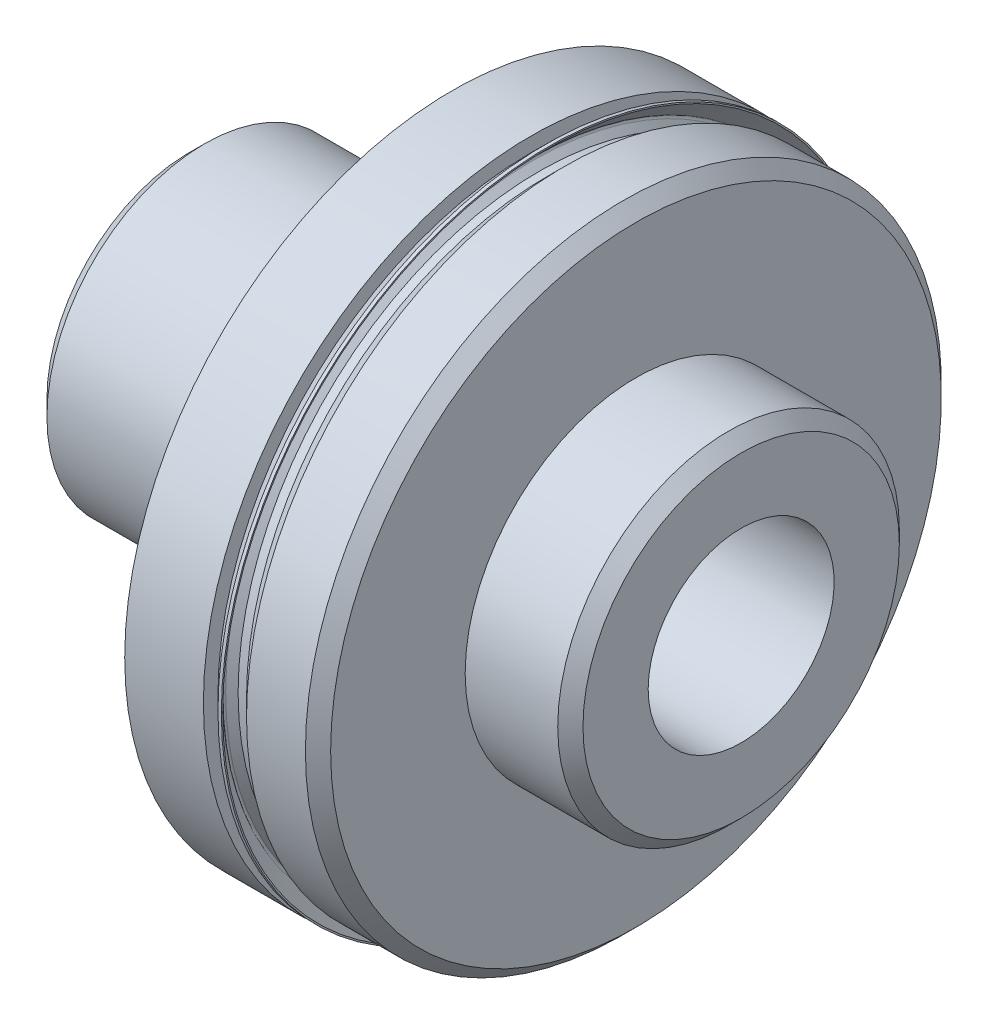
SolidWorks part; units mm, degrees
material "Cast Alloy Steel"
ref_plane "Front Plane" through (0, 0, 0) normal (0, 0, 1) x (1, 0, 0)
ref_plane "Top Plane" through (0, 0, 0) normal (0, 1, 0) x (1, 0, 0)
ref_plane "Right Plane" through (0, 0, 0) normal (1, 0, 0) x (0, 0, -1)
sketch "Sketch1" plane through (0, 0, 0) normal (0, 0, 1) x (1, 0, 0)
  line L0 (0, 0) -> (0, 8.589)
  line L1 (0, 8.589) -> (0.936, 9.525)
  line L2 (0.936, 9.525) -> (9.31, 9.525)
  line L3 (9.31, 9.525) -> (10.2623, 8.6108)
  line L4 (11.0363, 8.2995) -> (12.3698, 8.2995)
  line L5 (13.4874, 9.417) -> (13.4874, 9.4932)
  line L6 (13.4874, 9.4932) -> (15.875, 9.4932)
  line L7 (15.875, 9.4932) -> (15.875, 0)
  line L8 (15.875, 0) -> (0, 0)
  line L9 (15.875, 0) -> (0, 0) construction
  arc A0 (10.2623, 8.6108) -> (11.0363, 8.2995) centre (11.0363, 9.417) ccw
  arc A1 (12.3698, 8.2995) -> (13.4874, 9.417) centre (12.3698, 9.4171) ccw
revolve "Revolve1" add sketch "Sketch1" angle 360 about L9 reverse direction yes
cosmetic thread "Cosmetic Thread1" parameters "D1"=10.246, "D2"=17.178
sketch "Sketch2" plane through (0, 0, 0) normal (0, 0, 1) x (1, 0, 0)
  line L0 (15.875, 0) -> (15.875, 19.7676)
  line L1 (15.875, 19.7676) -> (20.6248, 19.7676)
  line L2 (20.6248, 19.7676) -> (20.6248, 18.1801)
  line L3 (20.6248, 18.1801) -> (21.6408, 18.1801)
  line L4 (21.6408, 18.1801) -> (22.6568, 19.196)
  line L5 (22.6568, 19.196) -> (26.2128, 19.196)
  line L6 (26.2128, 19.196) -> (26.9748, 18.434)
  line L7 (26.9748, 18.434) -> (26.9748, 0)
  line L8 (26.9748, 0) -> (15.875, 0)
  line L9 (26.9748, 0) -> (15.875, 0) construction
revolve "Revolve2" add sketch "Sketch2" angle 360 about L9 reverse direction yes
sketch "Sketch3" plane through (0, 0, 0) normal (0, 0, 1) x (1, 0, 0)
  line L0 (26.9748, 0) -> (26.9748, 10.3124)
  line L1 (26.9748, 10.3124) -> (32.5628, 10.3124)
  line L2 (32.5628, 10.3124) -> (33.3248, 9.5504)
  line L3 (33.3248, 9.5504) -> (33.3248, 0)
  line L4 (33.3248, 0) -> (26.9748, 0)
  line L5 (33.3248, 0) -> (26.9748, 0) construction
revolve "Revolve3" add sketch "Sketch3" angle 360 about L5 reverse direction yes
hole_wizard "Hole1" positions "Sketch5" profile "Sketch4" legacy
sketch "Sketch5" plane through (0, 0, 0) normal (-1, 0, 0) x (0, 0, 1)
  point P0 (0, 0)
sketch "Sketch4" plane through (0, 0, 0) normal (0, 1, 0) x (0, 0, 1)
  line L0 (0, 0) -> (0, 33.3248)
  line L1 (0, 33.3248) -> (5.6134, 33.3248)
  line L2 (5.6134, 33.3248) -> (5.6134, 0.762)
  line L3 (5.6134, 0.762) -> (6.3754, 0)
  line L4 (6.3754, 0) -> (0, 0)
  line L5 (0, -6.4453) -> (0, 115.525) construction
  line L6 (-5.6134, 0.762) -> (-6.3754, 0) construction
  dimension "Diameter" = 11.2268
  dimension "Depth" = 33.3248
  dimension "C-Sink Angle" = 90
  dimension "C-Sink Diameter" = 12.7508
ref_plane "Plane1" through (25.527, 0, 0) normal (1, 0, 0) x (0, 0, -1)
ref_plane "Plane2" through (25.527, 0, 0) normal (1, 0, 0) x (0, 0, -1)
ref_plane "Plane3" through (0, 0, 0) normal (0, -0.7071, 0.7071) x (1, 0, 0)
ref_plane "Plane4" through (3.1242, 0, 0) normal (1, 0, 0) x (0, 0, -1)
ref_plane "Plane5" through (20.6502, 0, 0) normal (1, 0, 0) x (0, 0, -1)
ref_plane "Plane6" through (15.875, 0, 0) normal (1, 0, 0) x (0, 0, -1)
ref_plane "Plane7" through (20.6502, 0, 0) normal (1, 0, 0) x (0, 0, -1)
sketch "Sketch6" plane through (0, 0, 0) normal (0, 0, 1) x (1, 0, 0)
  line L0 (20.6248, 17.9261) -> (21.6408, 17.9261)
  line L1 (21.6408, 17.9261) -> (21.6408, 18.1801)
  line L2 (21.6408, 18.1801) -> (21.1328, 18.1801)
  line L3 (21.1328, 18.1801) -> (20.7582, 18.5547)
  line L4 (20.7582, 18.7343) -> (21.7073, 19.6834)
  line L5 (21.7073, 19.6834) -> (21.7073, 19.7676)
  line L6 (21.7073, 19.7676) -> (21.5041, 19.7676)
  line L7 (21.5041, 19.7676) -> (20.6248, 18.8883)
  line L8 (20.6248, 18.8883) -> (20.6248, 17.9261)
  line L9 (21.6408, 0) -> (20.6248, 0) construction
  arc A0 (20.7582, 18.5547) -> (20.7582, 18.7343) centre (20.848, 18.6445) cw
revolve "Revolve4" add sketch "Sketch6" angle 360 about L9 reverse direction yes
ref_plane "Plane8" through (21.6408, 0, 0) normal (1, 0, 0) x (0, 0, -1)
ref_plane "Plane9" through (15.875, 0, 0) normal (1, 0, 0) x (0, 0, -1)
ref_plane "Plane10" through (13.4874, 0, 0) normal (1, 0, 0) x (0, 0, -1)
ref_plane "Plane11" through (0, 22.225, 0) normal (0, 1, 0) x (-1, 0, 0)
ref_plane "Plane12" through (0, -22.225, 0) normal (0, 1, 0) x (-1, 0, 0)
ref_plane "Plane13" through (15.875, 0, 0) normal (1, 0, 0) x (0, 0, -1)
ref_plane "Plane14" through (0, 0, 0) normal (0, 1, 0) x (-1, 0, 0)
ref_plane "Plane15" through (0, 0, 0) normal (0, 1, 0) x (-1, 0, 0)
ref_plane "Plane16" through (0, 14.2875, 0) normal (0, 1, 0) x (-1, 0, 0)
ref_plane "Plane17" through (0, 0, 0) normal (1, 0, 0) x (0, 0, -1)
ref_plane "dp1 XY" through (0, 0, 0) normal (0, 0, 1) x (1, 0, 0)
ref_plane "dp1 XZ" through (0, 9.4932, 0) normal (0, -1, 0) x (1, 0, 0)
ref_plane "dp1 YZ" through (15.875, 0, 0) normal (1, 0, 0) x (0, 0, -1)
ref_axis "dp1 X" through (-80.9, 9.4932, 0) along (1, 0, 0)
ref_axis "dp1 Y" through (15.875, -50, 0) along (0, 1, 0)
ref_axis "dp1 Z" through (15.875, 9.4932, 80.9) along (0, 0, -1)
sketch3d "dp1"
  point P0 (15.875, 9.4932, 0)
ref_plane "dp2 XY" through (0, 0, 0) normal (0, 0, 1) x (1, 0, 0)
ref_plane "dp2 XZ" through (0, -9.4932, 0) normal (0, -1, 0) x (1, 0, 0)
ref_plane "dp2 YZ" through (15.875, 0, 0) normal (1, 0, 0) x (0, 0, -1)
ref_axis "dp2 X" through (-80.9, -9.4932, 0) along (1, 0, 0)
ref_axis "dp2 Y" through (15.875, -50, 0) along (0, 1, 0)
ref_axis "dp2 Z" through (15.875, -9.4932, 80.9) along (0, 0, -1)
sketch3d "dp2"
  point P0 (15.875, -9.4932, 0)
ref_plane "rod_guide XY" through (0, 0, 0) normal (1, 0, 0) x (0, 0, -1)
ref_plane "rod_guide XZ" through (0, 0, 0) normal (0, -1, 0) x (1, 0, 0)
ref_plane "rod_guide YZ" through (0, 0, 0) normal (0, 0, -1) x (-1, 0, 0)
ref_axis "rod_guide X" through (0, 0, 80.9) along (0, 0, -1)
ref_axis "rod_guide Y" through (0, -50, 0) along (0, 1, 0)
ref_axis "rod_guide Z" through (80.9, 0, 0) along (-1, 0, 0)
sketch3d "rod_guide"
  point P0 (0, 0, 0)
ref_plane "s1 XY" through (0, 0, 0) normal (0, 0, 1) x (1, 0, 0)
ref_plane "s1 XZ" through (0, 0, 0) normal (0, -1, 0) x (1, 0, 0)
ref_plane "s1 YZ" through (13.4874, 0, 0) normal (1, 0, 0) x (0, 0, -1)
ref_axis "s1 X" through (-80.9, 0, 0) along (1, 0, 0)
ref_axis "s1 Y" through (13.4874, -50, 0) along (0, 1, 0)
ref_axis "s1 Z" through (13.4874, 0, 80.9) along (0, 0, -1)
sketch3d "s1"
  point P0 (13.4874, 0, 0)
ref_plane "s2 XY" through (0, 0, 0) normal (0, 0, 1) x (1, 0, 0)
ref_plane "s2 XZ" through (0, 0, 0) normal (0, -1, 0) x (1, 0, 0)
ref_plane "s2 YZ" through (15.875, 0, 0) normal (1, 0, 0) x (0, 0, -1)
ref_axis "s2 X" through (-80.9, 0, 0) along (1, 0, 0)
ref_axis "s2 Y" through (15.875, -50, 0) along (0, 1, 0)
ref_axis "s2 Z" through (15.875, 0, 80.9) along (0, 0, -1)
sketch3d "s2"
  point P0 (15.875, 0, 0)
ref_plane "t1 XY" through (15.875, 0, 0) normal (1, 0, 0) x (0, 0, -1)
ref_plane "t1 XZ" through (0, 0, 0) normal (0, -1, 0) x (1, 0, 0)
ref_plane "t1 YZ" through (0, 0, 0) normal (0, 0, -1) x (-1, 0, 0)
ref_axis "t1 X" through (15.875, 0, 80.9) along (0, 0, -1)
ref_axis "t1 Y" through (15.875, -50, 0) along (0, 1, 0)
ref_axis "t1 Z" through (80.9, 0, 0) along (-1, 0, 0)
sketch3d "t1"
  point P0 (15.875, 0, 0)
ref_plane "t111 XY" through (15.875, 0, 0) normal (1, 0, 0) x (0, 0, -1)
ref_plane "t111 XZ" through (0, 0, 0) normal (0, -1, 0) x (1, 0, 0)
ref_plane "t111 YZ" through (0, 0, 0) normal (0, 0, -1) x (-1, 0, 0)
ref_axis "t111 X" through (15.875, 0, 80.9) along (0, 0, -1)
ref_axis "t111 Y" through (15.875, -50, 0) along (0, 1, 0)
ref_axis "t111 Z" through (80.9, 0, 0) along (-1, 0, 0)
sketch3d "t111"
  point P0 (15.875, 0, 0)
ref_plane "to_foot_bracket XY" through (15.875, 0, 0) normal (1, 0, 0) x (0, 0, -1)
ref_plane "to_foot_bracket XZ" through (0, 0, 0) normal (0, -1, 0) x (1, 0, 0)
ref_plane "to_foot_bracket YZ" through (0, 0, 0) normal (0, 0, -1) x (-1, 0, 0)
ref_axis "to_foot_bracket X" through (15.875, 0, 80.9) along (0, 0, -1)
ref_axis "to_foot_bracket Y" through (15.875, -50, 0) along (0, 1, 0)
ref_axis "to_foot_bracket Z" through (80.9, 0, 0) along (-1, 0, 0)
sketch3d "to_foot_bracket"
  point P0 (15.875, 0, 0)
ref_plane "to_nut XY" through (13.4874, 0, 0) normal (1, 0, 0) x (0, 0, -1)
ref_plane "to_nut XZ" through (0, 0, 0) normal (0, -1, 0) x (1, 0, 0)
ref_plane "to_nut YZ" through (0, 0, 0) normal (0, 0, -1) x (-1, 0, 0)
ref_axis "to_nut X" through (13.4874, 0, 80.9) along (0, 0, -1)
ref_axis "to_nut Y" through (13.4874, -50, 0) along (0, 1, 0)
ref_axis "to_nut Z" through (80.9, 0, 0) along (-1, 0, 0)
sketch3d "to_nut"
  point P0 (13.4874, 0, 0)
ref_plane "to_rod XY" through (0, 0, 0) normal (1, 0, 0) x (0, 0, -1)
ref_plane "to_rod XZ" through (0, 0, 0) normal (0, -1, 0) x (1, 0, 0)
ref_plane "to_rod YZ" through (0, 0, 0) normal (0, 0, -1) x (-1, 0, 0)
ref_axis "to_rod X" through (0, 0, 80.9) along (0, 0, -1)
ref_axis "to_rod Y" through (0, -50, 0) along (0, 1, 0)
ref_axis "to_rod Z" through (80.9, 0, 0) along (-1, 0, 0)
sketch3d "to_rod"
  point P0 (0, 0, 0)
ref_plane "to_screw XY" through (0, 14.2875, 0) normal (0, 1, 0) x (-1, 0, 0)
ref_plane "to_screw XZ" through (0, 0, -10.0711) normal (0, 0, 1) x (1, 0, 0)
ref_plane "to_screw YZ" through (17.4498, 0, 0) normal (1, 0, 0) x (0, 0, -1)
ref_axis "to_screw X" through (-80.9, 14.2875, -10.0711) along (1, 0, 0)
ref_axis "to_screw Y" through (17.4498, 14.2875, 50) along (0, 0, -1)
ref_axis "to_screw Z" through (17.4498, 50, -10.0711) along (0, -1, 0)
sketch3d "to_screw"
  point P0 (17.4498, 14.2875, -10.0711)
ref_plane "to_trunnion_brackets XY" through (0, 0, 0) normal (0, 1, 0) x (-1, 0, 0)
ref_plane "to_trunnion_brackets XZ" through (0, 0, 0) normal (0, 0, 1) x (1, 0, 0)
ref_plane "to_trunnion_brackets YZ" through (26.9494, 0, 0) normal (1, 0, 0) x (0, 0, -1)
ref_axis "to_trunnion_brackets X" through (-80.9, 0, 0) along (1, 0, 0)
ref_axis "to_trunnion_brackets Y" through (26.9494, 0, 50) along (0, 0, -1)
ref_axis "to_trunnion_brackets Z" through (26.9494, 50, 0) along (0, -1, 0)
sketch3d "to_trunnion_brackets"
  point P0 (26.9494, 0, 0)
ref_plane "to_trunnion_brackets1 XY" through (0, 22.225, 0) normal (0, 1, 0) x (-1, 0, 0)
ref_plane "to_trunnion_brackets1 XZ" through (0, 0, 0) normal (0, 0, 1) x (1, 0, 0)
ref_plane "to_trunnion_brackets1 YZ" through (26.9494, 0, 0) normal (1, 0, 0) x (0, 0, -1)
ref_axis "to_trunnion_brackets1 X" through (-80.9, 22.225, 0) along (1, 0, 0)
ref_axis "to_trunnion_brackets1 Y" through (26.9494, 22.225, 50) along (0, 0, -1)
ref_axis "to_trunnion_brackets1 Z" through (26.9494, 50, 0) along (0, -1, 0)
sketch3d "to_trunnion_brackets1"
  point P0 (26.9494, 22.225, 0)
ref_plane "to_trunnion_brackets2 XY" through (0, -22.225, 0) normal (0, 1, 0) x (-1, 0, 0)
ref_plane "to_trunnion_brackets2 XZ" through (0, 0, 0) normal (0, 0, 1) x (1, 0, 0)
ref_plane "to_trunnion_brackets2 YZ" through (26.9494, 0, 0) normal (1, 0, 0) x (0, 0, -1)
ref_axis "to_trunnion_brackets2 X" through (-80.9, -22.225, 0) along (1, 0, 0)
ref_axis "to_trunnion_brackets2 Y" through (26.9494, -22.225, 50) along (0, 0, -1)
ref_axis "to_trunnion_brackets2 Z" through (26.9494, 50, 0) along (0, -1, 0)
sketch3d "to_trunnion_brackets2"
  point P0 (26.9494, -22.225, 0)
ref_plane "to_tube XY" through (21.6408, 0, 0) normal (1, 0, 0) x (0, 0, -1)
ref_plane "to_tube XZ" through (0, 0, 0) normal (0, -1, 0) x (1, 0, 0)
ref_plane "to_tube YZ" through (0, 0, 0) normal (0, 0, -1) x (-1, 0, 0)
ref_axis "to_tube X" through (21.6408, 0, 80.9) along (0, 0, -1)
ref_axis "to_tube Y" through (21.6408, -50, 0) along (0, 1, 0)
ref_axis "to_tube Z" through (80.9, 0, 0) along (-1, 0, 0)
sketch3d "to_tube"
  point P0 (21.6408, 0, 0)
